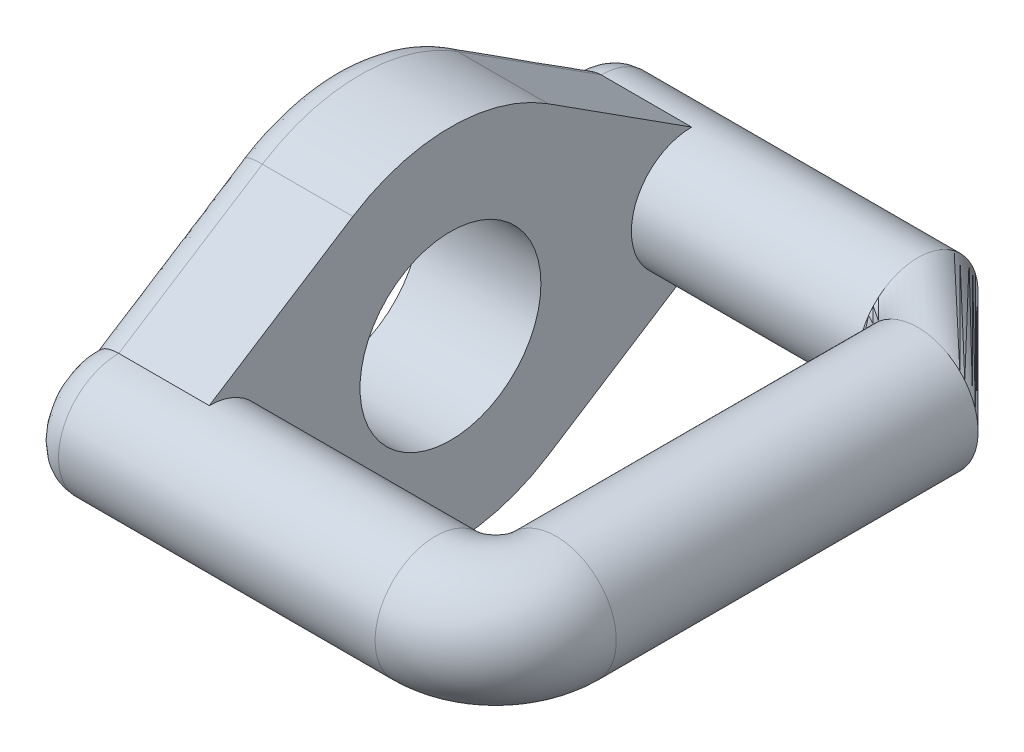
SolidWorks part; units mm, degrees
material "Aleación 1060"
ref_plane "Alzado" through (0, 0, 0) normal (0, 0, 1) x (1, 0, 0)
ref_plane "Planta" through (0, 0, 0) normal (0, 1, 0) x (1, 0, 0)
ref_plane "Vista lateral" through (0, 0, 0) normal (1, 0, 0) x (0, 0, -1)
sketch "Croquis1" plane through (0, 0, 0) normal (1, 0, 0) x (0, 0, -1)
  line L2 (8, 2) -> (3.237, 5.0519)
  line L3 (-8, 2) -> (-3.237, 5.0519)
  line L5 (-3.237, -5.0519) -> (-8, -2)
  line L7 (3.237, -5.0519) -> (8, -2)
  arc A0 (3.237, 5.0519) -> (-3.237, 5.0519) centre (0, 0) ccw
  circle A1 centre (0, 0) radius 3
  arc A2 (8, -2) -> (8, 2) centre (8, 0) ccw
  arc A3 (-8, 2) -> (-8, -2) centre (-8, 0) ccw
  arc A4 (-3.237, -5.0519) -> (3.237, -5.0519) centre (0, 0) ccw
  dimension "D1" = 8
  dimension "D2" = 6
  dimension "D4" = 2
  dimension "D5" = 2
  dimension "D3" = 8
extrude "Saliente-Extruir1" add sketch "Croquis1" along normal blind 4
fillet "Redondeo1" radius 1 8 edges at (0, 3.5259, 5.6185) (0, 0, 10) (0, -3.5259, 5.6185) (0, -6, 0) (0, -3.5259, -5.6185) (0, 0, -10) (0, 3.5259, -5.6185) (0, 6, 0) first distance on face at (0, 0, 0)
sketch "Croquis136" plane through (0, 0, 0) normal (0, 1, 0) x (1, 0, 0)
  line L2 (4, 8) -> (11.5, 8)
  line L3 (13.5, 6) -> (13.5, -6)
  line L4 (11.5, -8) -> (4, -8)
  arc A0 (13.5, 6) -> (11.5, 8) centre (11.5, 6) ccw
  arc A1 (11.5, -8) -> (13.5, -6) centre (11.5, -6) ccw
sweep "Barrer10" add path "Croquis136" circular profile diameter 4 parameters "D3"=4
